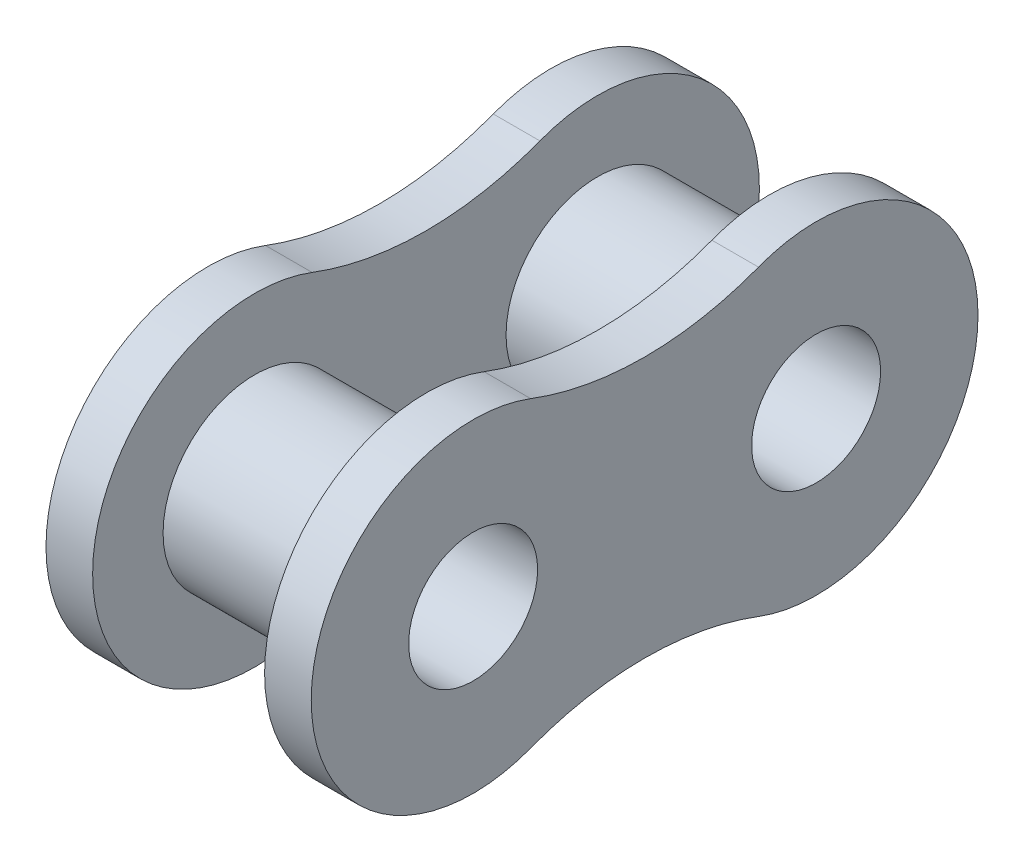
SolidWorks part; units mm, degrees
ref_plane "Front" through (0, 0, 0) normal (0, 0, 1) x (1, 0, 0)
ref_plane "Top" through (0, 0, 0) normal (0, 1, 0) x (1, 0, 0)
ref_plane "Right" through (0, 0, 0) normal (1, 0, 0) x (0, 0, -1)
sketch "Sketch1" plane through (0, 0, 0) normal (1, 0, 0) x (0, 0, -1)
  line L0 (0, 0) -> (9.525, 0) construction
  arc A0 (1.5995, 4.2016) -> (1.5995, -4.2016) centre (0, 0) ccw
  arc A1 (7.9255, -4.2016) -> (7.9255, 4.2016) centre (9.525, 0) ccw
  arc A2 (1.5995, 4.2016) -> (7.9255, 4.2016) centre (4.7625, 12.5099) ccw
  arc A3 (1.5995, -4.2016) -> (7.9255, -4.2016) centre (4.7625, -12.5099) cw
  circle A4 centre (0, 0) radius 2.54
  circle A5 centre (9.525, 0) radius 2.54
  circle A6 centre (9.525, 0) radius 1.7907
  circle A7 centre (0, 0) radius 1.7907
  dimension "D1" = 8.9916
  dimension "D2" = 9.525
  dimension "D3" = 8.89
  dimension "D4" = 5.08
  dimension "D5" = 3.5814
extrude "Boss-Extrude1" add sketch "Sketch1" along normal mid plane 4.7752 contours A5 | A4 region at (0, 0, 2.4682) region at (0, 0, -7.0568)
extrude "Boss-Extrude2" add sketch "Sketch1<4>" along normal blind 1.2954 from surface contours A0 A3 A1 A2 A4 A5 | A7 A4 | A5 A6 region at (0, 0, -4.7625) region at (0, 0, 2.4682) region at (0, 0, -7.0568) starting at face at (2.3876, 0, -11.3157)
sketch "Sketch1<4>" plane through (0, 0, 0) normal (1, 0, 0) x (0, 0, -1) same geometry as "Sketch1"
extrude "Boss-Extrude3" add sketch "Sketch1<5>" against normal blind 1.2954 from surface separate body contours A0 A3 A1 A2 A4 A5 | A5 A6 | A7 A4 region at (0, 0, -4.7625) region at (0, 0, 2.4682) region at (0, 0, -7.0568) starting at face at (-2.3876, 0, -11.3157)
sketch "Sketch1<5>" plane through (0, 0, 0) normal (1, 0, 0) x (0, 0, -1) same geometry as "Sketch1"
